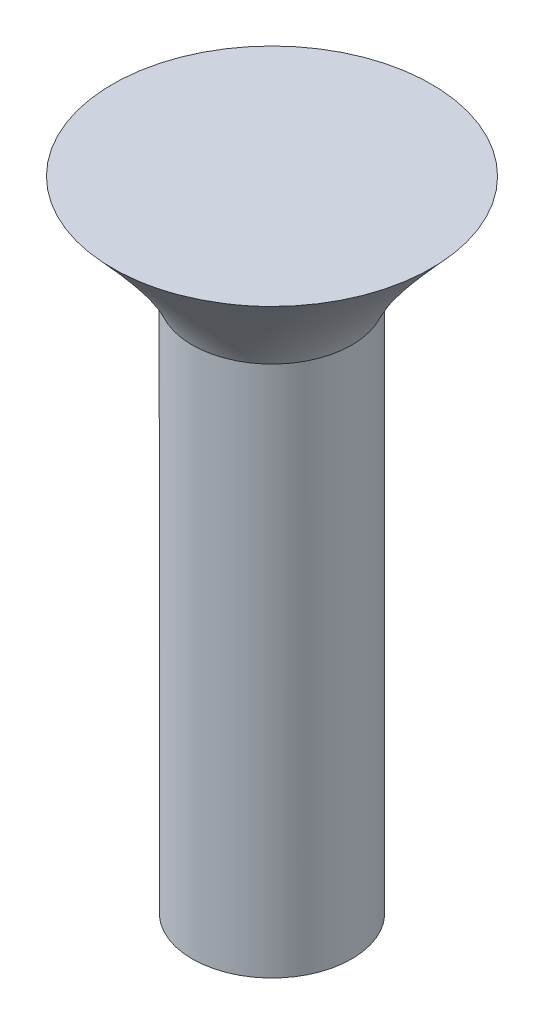
SolidWorks part; units mm, degrees
ref_plane "Front Plane" through (0, 0, 0) normal (0, 0, 1) x (1, 0, 0)
ref_plane "Top Plane" through (0, 0, 0) normal (0, 1, 0) x (1, 0, 0)
ref_plane "Right Plane" through (0, 0, 0) normal (1, 0, 0) x (0, 0, -1)
sketch "Sketch1" plane through (0, 0, 0) normal (0, 1, 0) x (1, 0, 0)
  circle A0 centre (0, 0) radius 3
  dimension "D1" = 6
extrude "Boss-Extrude1" add sketch "Sketch1" along normal blind 20
ref_plane "Plane1" through (0, 24, 0) normal (0, 1, 0) x (1, 0, 0)
sketch "Sketch2" plane through (0, 24, 0) normal (0, 1, 0) x (1, 0, 0)
  circle A0 centre (0, 0) radius 6
  dimension "D1" = 12
sketch "Sketch3" plane through (0, 20, 0) normal (0, 1, 0) x (1, 0, 0)
  circle A1 centre (0, 0) radius 3
  circle A2 centre (0, 0) radius 3
  dimension "D1" = 0
loft "Loft1" add profiles "Sketch3", "Sketch2" connector at (-2.7342, 20, -1.2345) connector at (-2.7038, 24, -5.3563)
